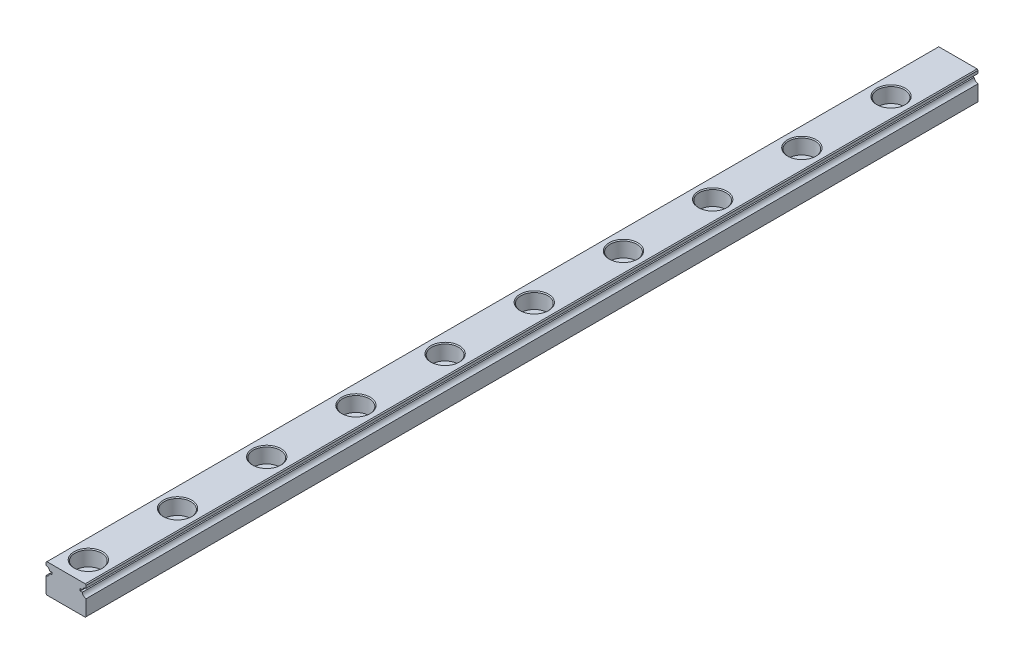
SolidWorks part; units mm, degrees
material "Acero inoxidable (ferrítico)"
ref_plane "Спереди" through (0, 0, 0) normal (0, 0, 1) x (1, 0, 0)
ref_plane "Сверху" through (0, 0, 0) normal (0, 1, 0) x (1, 0, 0)
ref_plane "Справа" through (0, 0, 0) normal (1, 0, 0) x (0, 0, -1)
sketch "Sketch1" plane through (0, 0, 0) normal (0, 0, 1) x (1, 0, 0)
  line L0 (0, 0) -> (0, 4.3706) construction
  line L1 (-4.3, -3.25) -> (4.3, -3.25)
  line L2 (-4.5, -3.05) -> (-4.5, 0.455)
  line L3 (-4.3, 3.25) -> (4.3, 3.25)
  line L4 (4.5, -3.05) -> (4.5, 0.455)
  line L5 (-4.5, -3.25) -> (4.5, 3.25) construction
  line L6 (-4.5, 3.25) -> (4.5, -3.25) construction
  line L7 (-4.5, 2.445) -> (-4.5, 3.05)
  line L8 (4.5, 2.445) -> (4.5, 3.05)
  line L9 (-4.5, -3.05) -> (-4.3, -3.25)
  line L10 (4.3, -3.25) -> (4.5, -3.05)
  line L11 (4.3, 3.25) -> (4.5, 3.05)
  line L12 (-4.5, 3.05) -> (-4.3, 3.25)
  line L13 (3.6177, 1.2625) -> (3.1501, 1.2625)
  line L14 (-3.6177, 1.2625) -> (-3.1501, 1.2625)
  line L15 (3.1501, 1.2625) -> (3.1501, 1.7625)
  line L16 (-3.6501, 1.7625) -> (-3.1501, 1.7625)
  line L17 (-3.1501, 1.2625) -> (-3.1501, 1.7625)
  line L18 (3.6501, 1.7625) -> (3.1501, 1.7625)
  arc A0 (-4.5, 2.445) -> (-3.6501, 1.7625) centre (-4.6, 1.45) cw
  arc A1 (4.5, 2.445) -> (3.6501, 1.7625) centre (4.6, 1.45) ccw
  arc A2 (-3.6177, 1.2625) -> (-4.5, 0.455) centre (-4.6, 1.45) cw
  arc A3 (3.6177, 1.2625) -> (4.5, 0.455) centre (4.6, 1.45) ccw
  point P0 (0, 0)
  dimension "D4" = 1
  dimension "D5" = 0.1
  dimension "D1" = 9
  dimension "D2" = 6.5
  dimension "D3" = 1.8
  dimension "D6" = 0.5
  dimension "D7" = 0.5
extrude "Extrude1" add sketch "Sketch1" along normal blind 200
sketch "Sketch2" plane through (0, 3.25, 0) normal (0, 1, 0) x (1, 0, 0)
  line L0 (0, 0) -> (0, -15) construction
  circle A0 centre (0, -15) radius 1.75
  circle A1 centre (0, -15) radius 3
  dimension "D1" = 3.5
  dimension "D2" = 6
  dimension "D3" = 15
extrude "Extrude2" cut sketch "Sketch2" against normal up to next contours A0 region at (0, 3.25, 15)
extrude "Extrude4" cut sketch "Sketch" against normal blind 3.5
sketch "Sketch" plane through (0, 3.25, 0) normal (0, 1, 0) x (1, 0, 0) same geometry as "Sketch2"
chamfer "Chamfer1" distance 0.2 angle 45 2 edges at (0, -3.25, 16.75) (0, 3.25, 18)
pattern_linear "LPattern1" count 10 spacing 20 along (0, 0, 1) of "Extrude4", "Chamfer1", "Extrude2"
